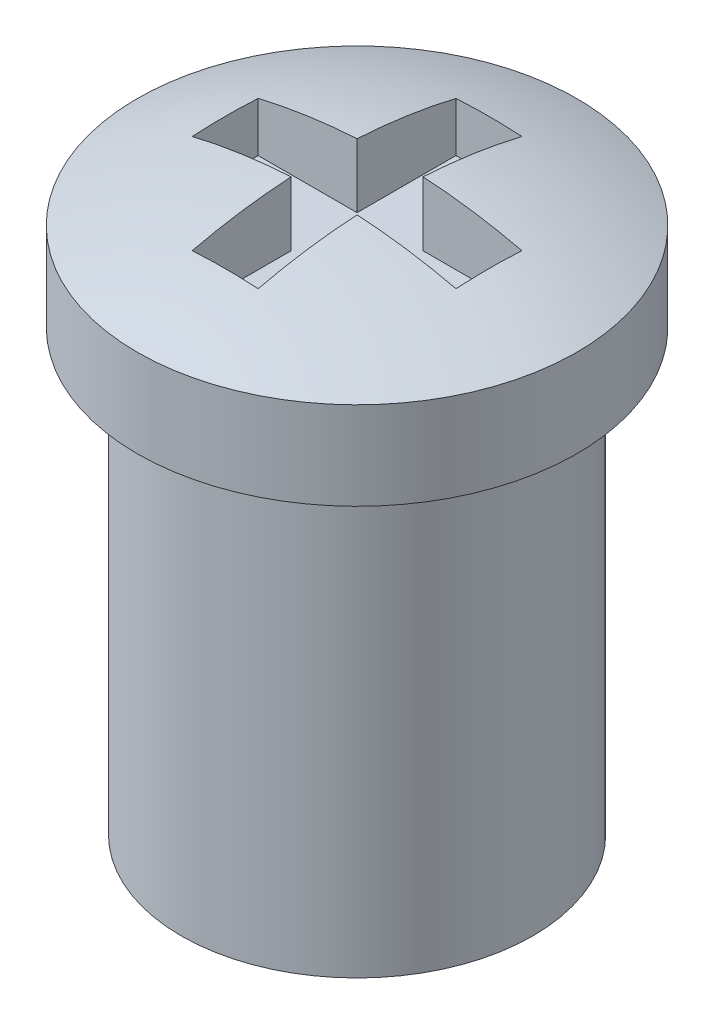
SolidWorks part; units mm, degrees
material "1023 Carbon Steel Sheet (SS)"
ref_plane "Front Plane" through (0, 0, 0) normal (0, 0, 1) x (1, 0, 0)
ref_plane "Top Plane" through (0, 0, 0) normal (0, 1, 0) x (1, 0, 0)
ref_plane "Right Plane" through (0, 0, 0) normal (1, 0, 0) x (0, 0, -1)
ref_plane "Top Plane1" through (0, 6.5, 0) normal (0, 1, 0) x (1, 0, 0)
sketch "Sketch1" plane through (0, 0, 0) normal (0, 1, 0) x (1, 0, 0)
  circle A0 centre (0, 0) radius 2
  dimension "D1" = 4
extrude "Boss-Extrude1" add sketch "Sketch1" along normal blind 5
sketch "Sketch2" plane through (0, 5, 0) normal (0, 1, 0) x (1, 0, 0)
  circle A0 centre (0, 0) radius 2.5
  dimension "D1" = 5
extrude "Boss-Extrude2" add sketch "Sketch2" along normal blind 1
dome "Dome1" faces to dome 1 distance 0.5 reverse direction no elliptical dome no face at (0, 6, 2.5) parameters "D1"=0.5
sketch "Sketch3" plane through (0, 6.5, 0) normal (0, 1, 0) x (1, 0, 0)
  line L0 (-2.5, 0) -> (2.5, 0) construction
  line L1 (0, 2.5) -> (0, -2.5) construction
  line L2 (-1.5, 0.375) -> (1.5, -0.375) construction
  line L3 (-1.5, 0.375) -> (1.5, 0.375)
  line L4 (-1.5, 0.375) -> (-1.5, -0.375)
  line L5 (-1.5, -0.375) -> (1.5, -0.375)
  line L6 (1.5, 0.375) -> (1.5, -0.375)
  line L7 (0.375, 1.5) -> (-0.375, -1.5) construction
  line L8 (-0.375, 1.5) -> (0.375, 1.5)
  line L9 (-0.375, 1.5) -> (-0.375, -1.5)
  line L10 (-0.375, -1.5) -> (0.375, -1.5)
  line L11 (0.375, 1.5) -> (0.375, -1.5)
  circle A0 centre (0, 0) radius 2.5 construction
  dimension "D1" = 1.5
  dimension "D2" = 1.5
  dimension "D3" = 0.75
  dimension "D4" = 0.75
extrude "Cut-Extrude1" cut sketch "Sketch3" against normal blind 0.75 contours L9 L3 L4 L5 | L11 L3 L9 L5 | L11 L8 L9 L3 | L3 L11 L5 L6 | L11 L5 L9 L10 region at (-0.9375, 6.5, 0) region at (0, 6.5, -0.9375) region at (0, 6.5, 0) region at (0.9375, 6.5, 0) region at (0, 6.5, 0.9375)
